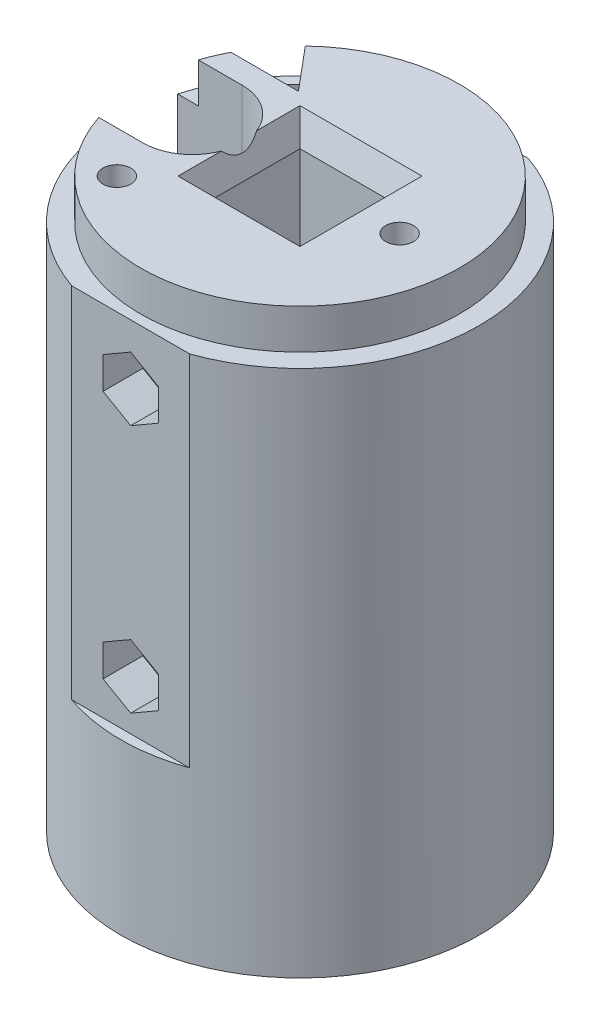
SolidWorks part; units mm, degrees
ref_plane "Спереди" through (0, 0, 0) normal (0, 0, 1) x (1, 0, 0)
ref_plane "Сверху" through (0, 0, 0) normal (0, 1, 0) x (1, 0, 0)
ref_plane "Справа" through (0, 0, 0) normal (1, 0, 0) x (0, 0, -1)
sketch "Sketch1" plane through (0, 0, 0) normal (0, 1, 0) x (1, 0, 0)
  line L0 (-5.125, 0) -> (-18, 0) construction
  line L1 (5.125, -5.125) -> (-5.125, -5.125)
  line L2 (5.125, -5.125) -> (5.125, 5.125)
  line L3 (5.125, 5.125) -> (-5.125, 5.125)
  line L4 (-5.125, -5.125) -> (-5.125, 5.125)
  line L5 (5.125, -5.125) -> (-5.125, 5.125) construction
  line L6 (5.125, 5.125) -> (-5.125, -5.125) construction
  circle A0 centre (0, 0) radius 18
  circle A1 centre (-12, 0) radius 2
  dimension "D1" = 36
  dimension "D3" = 6
  dimension "D2" = 10.25
extrude "Boss-Extrude1" add sketch "Sketch1" along normal blind 57
sketch "Sketch2" plane through (0, 57, 0) normal (0, 1, 0) x (1, 0, 0)
  line L0 (-10.8, 5) -> (-17.2916, 5)
  line L1 (-10.8, -5) -> (-17.2916, -5)
  line L2 (-5.125, 0) -> (-18, 0) construction
  line L3 (-5.125, 5.125) -> (-5.125, -5.125) construction
  circle A1 centre (0, 0) radius 18 construction
  arc A2 (-17.2916, 5) -> (-17.2916, -5) centre (0, 0) ccw
  arc A3 (-10.8, 5) -> (-10.8, -5) centre (-10.8, 0) cw
  point P12 (-5.8, 0)
  dimension "D1" = 5
extrude "Cut-Extrude1" cut sketch "Sketch2" against normal blind 27
sketch "Sketch4" plane through (0, 0, 0) normal (0, -1, 0) x (-1, 0, 0)
  line L0 (0, 0) -> (18, 21.4516) construction
  line L1 (0, 0) -> (18, -21.4516) construction
  line L2 (18, 21.4516) -> (18, -21.4516) construction
  line L3 (0, 0) -> (13.6996, 11.6756) construction
  line L4 (0, 0) -> (13.6996, -11.6756) construction
  line L5 (0, 0) -> (18, 0) construction
  line L6 (5.125, 5.125) -> (5.125, -5.125) construction
  line L7 (11.5702, 13.7888) -> (5.1423, 6.1284) construction
  line L8 (5.1423, 6.1284) -> (5.1423, -4.3826) construction
  line L9 (5.1423, -4.3826) -> (13.6996, -11.6756) construction
  line L10 (5.1423, 0.8729) -> (18.1354, 0.8729) construction
  line L12 (15.8104, 5.5479) -> (6.4604, 5.5479)
  line L13 (15.8104, 5.5479) -> (15.8104, -3.8021)
  line L14 (15.8104, -3.8021) -> (6.4604, -3.8021)
  line L15 (6.4604, 5.5479) -> (6.4604, -3.8021)
  line L16 (15.8104, 5.5479) -> (6.4604, -3.8021) construction
  line L17 (15.8104, -3.8021) -> (6.4604, 5.5479) construction
  arc A0 (13.6996, -11.6756) -> (11.5702, 13.7888) centre (0.5154, 0.0431) ccw construction
  circle A2 centre (0, 0) radius 18 construction
  point P2 (11, 0)
  point P5 (11.5702, 13.7888)
  point P7 (4.1157, 3.5076)
  point P8 (11.5702, -13.7888)
  point P11 (5.125, -6.1077)
  point P16 (11.1354, 0.8729)
  dimension "D5" = 10
  dimension "D1" = 100
  dimension "D2" = 3
  dimension "D3" = 3
  dimension "D4" = 9.35
  dimension "D6" = 7
extrude "Cut-Extrude3" cut sketch "Sketch4" against normal blind 20.4
sketch "Sketch5" plane through (0, 57, 0) normal (0, 1, 0) x (1, 0, 0)
  line L0 (0, 18) -> (0, -18) construction
  line L1 (5.9161, 17) -> (-5.9161, 17)
  line L2 (5.9161, -17) -> (-5.9161, -17)
  circle A0 centre (0, 0) radius 18 construction
  arc A1 (5.9161, 17) -> (-5.9161, 17) centre (0, 0) ccw
  arc A2 (5.9161, -17) -> (-5.9161, -17) centre (0, 0) cw
  point P11 (0, 17)
  dimension "D1" = 1
extrude "Cut-Extrude4" cut sketch "Sketch5" against normal blind 40
sketch "Sketch6" plane through (0, 0, -17) normal (0, 0, -1) x (-1, 0, 0)
  line L0 (0, 57) -> (0, 17) construction
  line L1 (5.9161, 57) -> (-5.9161, 57) construction
  line L2 (5.9161, 17) -> (-5.9161, 17) construction
  circle A0 centre (0, 47) radius 1.5
  circle A1 centre (0, 22) radius 1.5
  dimension "D1" = 3
  dimension "D2" = 10
  dimension "D3" = 5
extrude "Cut-Extrude5" cut sketch "Sketch6" against normal through all
sketch "Sketch7" plane through (0, 0, -17) normal (0, 0, -1) x (-1, 0, 0)
  circle A0 centre (0, 47) radius 3
  circle A1 centre (0, 22) radius 3
  dimension "D1" = 6
extrude "Cut-Extrude6" cut sketch "Sketch7" against normal blind 3
sketch "Sketch8" plane through (0, 0, 17) normal (0, 0, 1) x (1, 0, 0)
  line L0 (5.9161, 17) -> (5.9161, 57) construction
  line L1 (0, 43.8) -> (2.7713, 45.4)
  line L2 (2.7713, 45.4) -> (2.7713, 48.6)
  line L3 (2.7713, 48.6) -> (0, 50.2)
  line L4 (0, 50.2) -> (-2.7713, 48.6)
  line L5 (-2.7713, 48.6) -> (-2.7713, 45.4)
  line L6 (-2.7713, 45.4) -> (0, 43.8)
  line L9 (0, 18.8) -> (2.7713, 20.4)
  line L10 (2.7713, 20.4) -> (2.7713, 23.6)
  line L11 (2.7713, 23.6) -> (0, 25.2)
  line L12 (0, 25.2) -> (-2.7713, 23.6)
  line L13 (-2.7713, 23.6) -> (-2.7713, 20.4)
  line L14 (-2.7713, 20.4) -> (0, 18.8)
  circle A0 centre (0, 47) radius 3.2 construction
  circle A1 centre (0, 22) radius 3.2 construction
  dimension "D1" = 6.4
extrude "Cut-Extrude7" cut sketch "Sketch8" against normal blind 4
chamfer "Chamfer1" distance 1 angle 70 4 edges at (-5.125, 57, 0) (0, 57, -5.125) (0, 57, 5.125) (5.125, 57, 0) first distance on face at (-5.2523, 57, 0)
sketch "Sketch9" plane through (0, 0, 0) normal (0, -1, 0) x (1, 0, 0)
  line L0 (16.4542, -7.2979) -> (-16.4542, -7.2979) construction
  line L1 (-15.8104, -5.5479) -> (-6.4604, -5.5479) construction
  line L2 (-7.4542, -7.2979) -> (-15.4542, -7.2979)
  line L3 (-7.4542, -7.2979) -> (-11.6323, -12.2772)
  line L4 (5.125, -5.125) -> (-5.125, -5.125) construction
  circle A0 centre (0, 0) radius 18 construction
  arc A1 (-15.4542, -7.2979) -> (-11.6323, -12.2772) centre (0.5168, 1.0043) ccw
  point P10 (-11.4542, -7.2979)
  dimension "D8" = 18
  dimension "D1" = 1.75
  dimension "D2" = 5
  dimension "D3" = 6.5
  dimension "D4" = 50
  dimension "D5" = 8
  dimension "D6" = 2.1729
  dimension "D7" = 23.9084
extrude "Cut-Extrude8" cut sketch "Sketch9" against normal through all
sketch "Sketch12" plane through (0, 57, 0) normal (0, 1, 0) x (1, 0, 0)
  line L0 (18, 0) -> (-10.8, 0) construction
  line L1 (0, 0) -> (-12.7279, -12.7279) construction
  arc A0 (5.9161, -17) -> (5.9161, 17) centre (0, 0) ccw construction
  arc A1 (-17.2916, -5) -> (-5.9161, -17) centre (0, 0) ccw construction
  circle A2 centre (10, 0) radius 1.4
  circle A3 centre (-9.1924, -9.1924) radius 1.4
  dimension "D1" = 2.8
  dimension "D2" = 10
  dimension "D3" = 13
extrude "Cut-Extrude10" cut sketch "Sketch12" against normal blind 20
sketch "Sketch10" plane through (0, 57, 0) normal (0, 1, 0) x (1, 0, 0)
  circle A1 centre (0, 0) radius 18
  circle A2 centre (0, 0) radius 16
  arc A3 (-17.2916, -5) -> (-5.9161, -17) centre (0, 0) ccw construction
  dimension "D1" = 2
extrude "Cut-Extrude9" cut sketch "Sketch10" against normal blind 4
